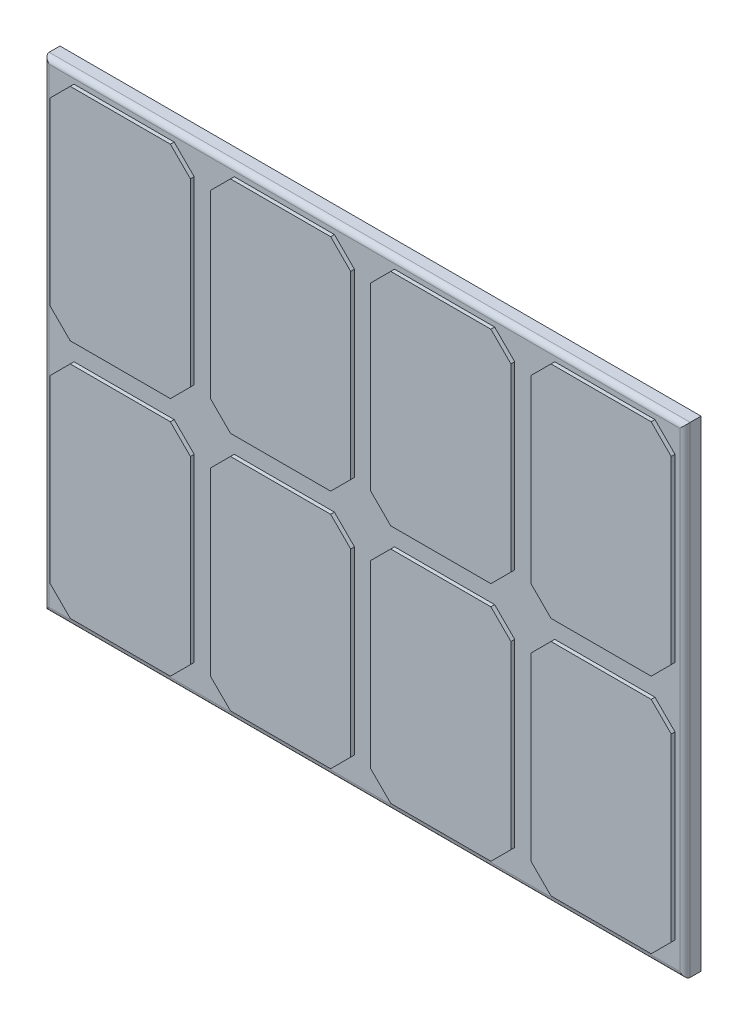
SolidWorks part; units mm, degrees
ref_plane "Front Plane" through (0, 0, 0) normal (0, 0, 1) x (1, 0, 0)
ref_plane "Top Plane" through (0, 0, 0) normal (0, 1, 0) x (1, 0, 0)
ref_plane "Right Plane" through (0, 0, 0) normal (1, 0, 0) x (0, 0, -1)
sketch "Sketch1" plane through (0, 0, 0) normal (0, 0, 1) x (1, 0, 0)
  line L1 (50.8, -38.1) -> (-50.8, -38.1)
  line L2 (50.8, -38.1) -> (50.8, 38.1)
  line L3 (50.8, 38.1) -> (-50.8, 38.1)
  line L4 (-50.8, -38.1) -> (-50.8, 38.1)
  line L5 (50.8, -38.1) -> (-50.8, 38.1) construction
  line L6 (50.8, 38.1) -> (-50.8, -38.1) construction
  point P0 (0, 0)
  dimension "D1" = 76.2
  dimension "D2" = 101.6
extrude "Boss-Extrude1" add sketch "Sketch1" along normal blind 2.54
sketch "Sketch2" plane through (0, 0, 2.54) normal (0, 0, 1) x (1, 0, 0)
  line L0 (-50.8, 38.1) -> (50.8, -38.1) construction
  line L1 (50.8, 38.1) -> (-50.8, -38.1) construction
  line L2 (0, 38.1) -> (0, -38.1) construction
  line L3 (50.8, 38.1) -> (-50.8, 38.1) construction
  line L4 (-50.8, -38.1) -> (50.8, -38.1) construction
  line L5 (-25.4, 38.1) -> (-25.4, -38.1) construction
  line L6 (25.4, -38.1) -> (25.4, 38.1) construction
  line L7 (-50.8, 0) -> (50.8, 0) construction
  line L8 (-50.8, 38.1) -> (-50.8, -38.1) construction
  line L9 (50.8, -38.1) -> (50.8, 38.1) construction
  line L10 (-50.8, 0) -> (-25.4, 38.1) construction
  line L11 (-46.0375, 36.5125) -> (-30.1625, 36.5125)
  line L12 (-49.2125, 33.3375) -> (-49.2125, 4.7625)
  line L13 (-46.0375, 1.5875) -> (-30.1625, 1.5875)
  line L14 (-26.9875, 33.3375) -> (-26.9875, 4.7625)
  line L15 (-49.2125, 36.5125) -> (-26.9875, 1.5875) construction
  line L16 (-49.2125, 1.5875) -> (-26.9875, 36.5125) construction
  line L17 (-46.0375, 36.5125) -> (-49.2125, 33.3375)
  line L18 (-30.1625, 36.5125) -> (-26.9875, 33.3375)
  line L19 (-26.9875, 4.7625) -> (-30.1625, 1.5875)
  line L20 (-49.2125, 4.7625) -> (-46.0375, 1.5875)
  line L21 (-23.8125, 33.3375) -> (-23.8125, 4.7625)
  line L22 (-23.8125, 4.7625) -> (-20.6375, 1.5875)
  line L23 (-20.6375, 36.5125) -> (-23.8125, 33.3375)
  line L24 (-20.6375, 36.5125) -> (-4.7625, 36.5125)
  line L25 (-4.7625, 36.5125) -> (-1.5875, 33.3375)
  line L26 (-1.5875, 33.3375) -> (-1.5875, 4.7625)
  line L27 (-1.5875, 4.7625) -> (-4.7625, 1.5875)
  line L28 (-20.6375, 1.5875) -> (-4.7625, 1.5875)
  line L29 (1.5875, 33.3375) -> (1.5875, 4.7625)
  line L30 (1.5875, 4.7625) -> (4.7625, 1.5875)
  line L31 (4.7625, 36.5125) -> (1.5875, 33.3375)
  line L32 (4.7625, 36.5125) -> (20.6375, 36.5125)
  line L33 (20.6375, 36.5125) -> (23.8125, 33.3375)
  line L34 (23.8125, 33.3375) -> (23.8125, 4.7625)
  line L35 (23.8125, 4.7625) -> (20.6375, 1.5875)
  line L36 (4.7625, 1.5875) -> (20.6375, 1.5875)
  line L37 (26.9875, 33.3375) -> (26.9875, 4.7625)
  line L38 (26.9875, 4.7625) -> (30.1625, 1.5875)
  line L39 (30.1625, 36.5125) -> (26.9875, 33.3375)
  line L40 (30.1625, 36.5125) -> (46.0375, 36.5125)
  line L41 (46.0375, 36.5125) -> (49.2125, 33.3375)
  line L42 (49.2125, 33.3375) -> (49.2125, 4.7625)
  line L43 (49.2125, 4.7625) -> (46.0375, 1.5875)
  line L44 (30.1625, 1.5875) -> (46.0375, 1.5875)
  line L45 (-23.8125, -4.7625) -> (-23.8125, -33.3375)
  line L46 (-23.8125, -33.3375) -> (-20.6375, -36.5125)
  line L47 (-20.6375, -1.5875) -> (-23.8125, -4.7625)
  line L48 (-20.6375, -1.5875) -> (-4.7625, -1.5875)
  line L49 (-4.7625, -1.5875) -> (-1.5875, -4.7625)
  line L50 (-1.5875, -4.7625) -> (-1.5875, -33.3375)
  line L51 (-1.5875, -33.3375) -> (-4.7625, -36.5125)
  line L52 (-20.6375, -36.5125) -> (-4.7625, -36.5125)
  line L53 (1.5875, -4.7625) -> (1.5875, -33.3375)
  line L54 (1.5875, -33.3375) -> (4.7625, -36.5125)
  line L55 (4.7625, -1.5875) -> (1.5875, -4.7625)
  line L56 (4.7625, -1.5875) -> (20.6375, -1.5875)
  line L57 (20.6375, -1.5875) -> (23.8125, -4.7625)
  line L58 (23.8125, -4.7625) -> (23.8125, -33.3375)
  line L59 (23.8125, -33.3375) -> (20.6375, -36.5125)
  line L60 (4.7625, -36.5125) -> (20.6375, -36.5125)
  line L61 (26.9875, -4.7625) -> (26.9875, -33.3375)
  line L62 (26.9875, -33.3375) -> (30.1625, -36.5125)
  line L63 (30.1625, -1.5875) -> (26.9875, -4.7625)
  line L64 (30.1625, -1.5875) -> (46.0375, -1.5875)
  line L65 (46.0375, -1.5875) -> (49.2125, -4.7625)
  line L66 (49.2125, -4.7625) -> (49.2125, -33.3375)
  line L67 (49.2125, -33.3375) -> (46.0375, -36.5125)
  line L68 (30.1625, -36.5125) -> (46.0375, -36.5125)
  line L69 (-49.2125, -4.7625) -> (-49.2125, -33.3375)
  line L70 (-49.2125, -33.3375) -> (-46.0375, -36.5125)
  line L71 (-46.0375, -1.5875) -> (-49.2125, -4.7625)
  line L72 (-46.0375, -1.5875) -> (-30.1625, -1.5875)
  line L73 (-30.1625, -1.5875) -> (-26.9875, -4.7625)
  line L74 (-26.9875, -4.7625) -> (-26.9875, -33.3375)
  line L75 (-26.9875, -33.3375) -> (-30.1625, -36.5125)
  line L76 (-46.0375, -36.5125) -> (-30.1625, -36.5125)
  point P24 (-38.1, 19.05)
  point P29 (-38.1, 19.05)
  dimension "D1" = 25.4
  dimension "D2" = 25.4
  dimension "D3" = 1.5875
  dimension "D4" = 1.5875
  dimension "D9" = 4
  dimension "D10" = 2
extrude "Boss-Extrude2" add sketch "Sketch2" along normal blind 0.5969
fillet "Fillet1" radius 0.8255 4 edges at (0, -38.1, 2.54) (50.8, 0, 2.54) (-50.8, 0, 2.54) (0, 38.1, 2.54)
